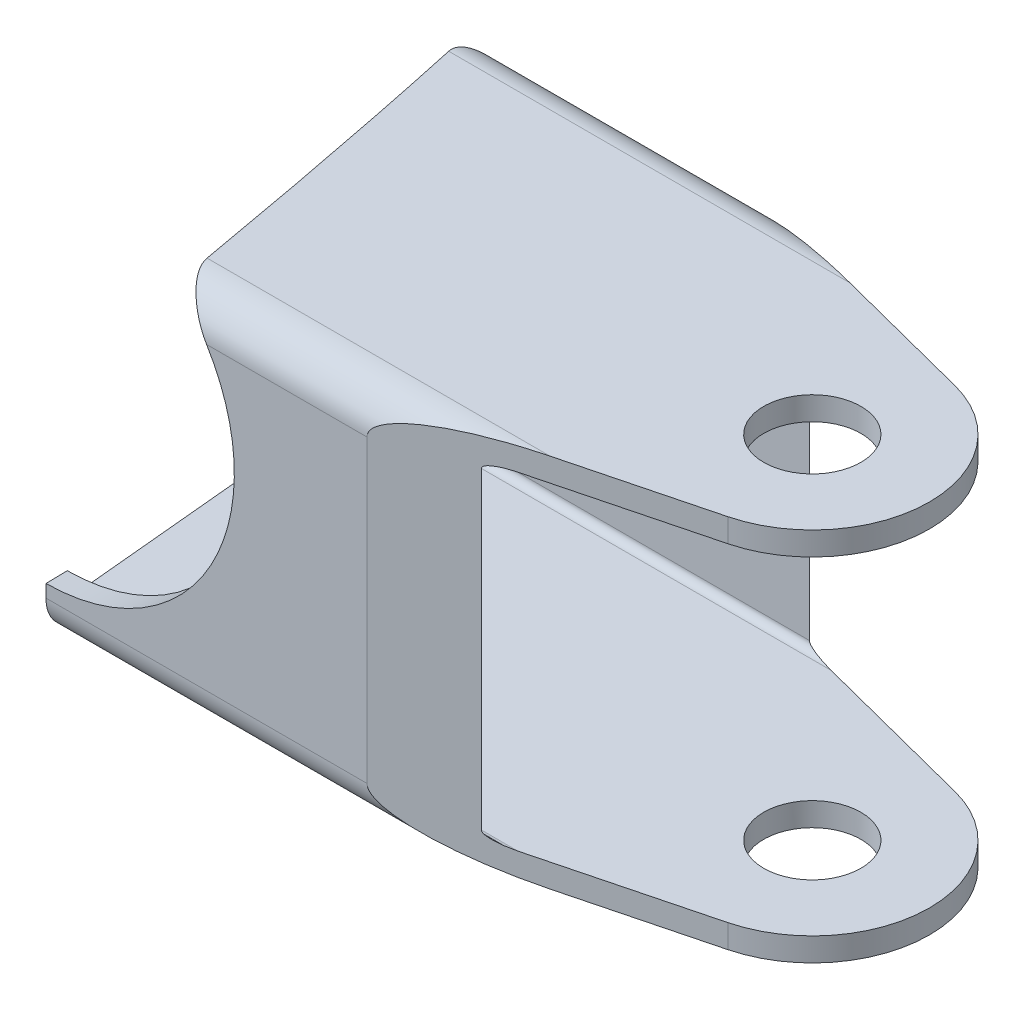
SolidWorks part; units mm, degrees
material "AISI 4130 Steel, annealed at 865C"
ref_plane "Front Plane" through (0, 0, 0) normal (0, 0, 1) x (1, 0, 0)
ref_plane "Top Plane" through (0, 0, 0) normal (0, 1, 0) x (1, 0, 0)
ref_plane "Right Plane" through (0, 0, 0) normal (1, 0, 0) x (0, 0, -1)
sketch "Sketch1" plane through (0, 0, 0) normal (1, 0, 0) x (0, 0, -1)
  line L1 (-10.16, 12.7) -> (10.16, 12.7)
  line L2 (-12.7, 10.16) -> (-12.7, -10.16)
  line L3 (-10.16, -12.7) -> (10.16, -12.7)
  line L4 (12.7, 10.16) -> (12.7, -10.16)
  arc A0 (-10.16, 12.7) -> (-12.7, 10.16) centre (-10.16, 10.16) ccw
  arc A1 (-10.16, -12.7) -> (-12.7, -10.16) centre (-10.16, -10.16) cw
  arc A2 (10.16, 12.7) -> (12.7, 10.16) centre (10.16, 10.16) cw
  arc A3 (12.7, -10.16) -> (10.16, -12.7) centre (10.16, -10.16) cw
  point P4 (0, -12.7)
  point P7 (0, 0)
  point P15 (12.7, 0)
  dimension "D3" = 2.54
  dimension "D4" = 2.54
  dimension "D5" = 2.54
  dimension "D6" = 2.54
  dimension "D1" = 25.4
  dimension "D2" = 20.32
extrude "Boss-Extrude1" add sketch "Sketch1" along normal blind 25.4 and the other way blind 34.925
sketch "Sketch11" plane through (25.4, 0, 0) normal (1, 0, 0) x (0, 0, -1)
  line L0 (-10.16, -12.7) -> (10.16, -12.7) construction
  line L1 (-10.6045, 11.1125) -> (10.6045, 11.1125)
  line L2 (-11.1125, 10.6045) -> (-11.1125, -10.6045)
  line L3 (-10.6045, -11.1125) -> (10.6045, -11.1125)
  line L4 (11.1125, 10.6045) -> (11.1125, -10.6045)
  line L5 (10.16, 12.7) -> (-10.16, 12.7) construction
  line L6 (12.7, -10.16) -> (12.7, 10.16) construction
  line L7 (-12.7, 10.16) -> (-12.7, -10.16) construction
  arc A0 (10.6045, 11.1125) -> (11.1125, 10.6045) centre (10.6045, 10.6045) cw
  arc A1 (10.6045, -11.1125) -> (11.1125, -10.6045) centre (10.6045, -10.6045) ccw
  arc A2 (-11.1125, -10.6045) -> (-10.6045, -11.1125) centre (-10.6045, -10.6045) ccw
  arc A3 (-10.6045, 11.1125) -> (-11.1125, 10.6045) centre (-10.6045, 10.6045) ccw
  dimension "D1" = 1.5875
  dimension "D2" = 1.5875
  dimension "D3" = 1.5875
  dimension "D4" = 1.5875
  dimension "D5" = 0.508
extrude "Cut-Extrude4" cut sketch "Sketch11" against normal through all
sketch "Sketch12" plane through (0, 12.7, 0) normal (0, 1, 0) x (1, 0, 0)
  line L1 (0, 12.7) -> (50.8, 12.7)
  line L2 (50.8, 12.7) -> (50.8, -12.7)
  line L12 (50.8, -12.7) -> (0, -12.7)
  line L13 (19.4444, -7.6861) -> (0, -12.7)
  line L14 (19.4444, 7.6861) -> (0, 12.7)
  line L15 (-34.925, -12.7) -> (25.4, -12.7) construction
  line L16 (-34.925, 12.7) -> (25.4, 12.7) construction
  line L18 (25.4, 10.16) -> (25.4, -10.16) construction
  arc A1 (19.4444, -7.6861) -> (19.4444, 7.6861) centre (17.4625, 0) ccw
  point P8 (18.1688, 9.2165)
  line M6 (-34.925, -10.16) -> (25.4, -10.16)
  line M7 (25.4, -10.16) -> (25.4, 10.16)
  line M8 (25.4, 10.16) -> (-34.925, 10.16)
  line M9 (-34.925, 10.16) -> (-34.925, -10.16)
  dimension "D2" = 50.8
  dimension "D1" = 17.4625
extrude "Cut-Extrude5" cut sketch "Sketch12" against normal through all contours M9 M8 M7 M6 | M7 M8 M9 | M6 M7 region at (34.888, 12.7, 0) region at (20.955, 12.7, -8.1283) region at (20.955, 12.7, 8.1283)
sketch "Sketch14" plane through (0, 12.7, 0) normal (0, 1, 0) x (1, 0, 0)
  circle A0 centre (17.4625, 0) radius 3.2893
  arc A2 (19.4444, -7.6861) -> (19.4444, 7.6861) centre (17.4625, 0) ccw construction
  point P0 (17.4625, 0)
  point P6 (25.4, 0)
  dimension "D2" = 6.5786
  dimension "D1" = 7.9375
  dimension "D3" = 17.4625
extrude "Cut-Extrude6" cut sketch "Sketch14" against normal through all
ref_axis "Axis1" through (-19.7119, 5.0326, 34.3014) along (-0.0934, -0.0736, -0.9929)
ref_point "Point2"
ref_plane "Plane1" through (-21.7437, 3.4321, 12.7) normal (-0.0934, -0.0736, -0.9929) x (-0.9956, 0.0069, 0.0931)
sketch "Sketch15" plane through (-21.7437, 3.4321, 12.7) normal (-0.0934, -0.0736, -0.9929) x (-0.9956, 0.0069, 0.0931)
  circle A0 centre (0, 0) radius 12.7
extrude "Cut-Extrude7" cut sketch "Sketch15" against normal through all both and the other way through all
ref_plane "Plane2" through (-22.7371, 0, 2.1386) normal (-0.9956, 0, 0.0936) x (-0.0934, -0.0736, -0.9929)
sketch "Sketch16" plane through (-22.7371, 0, 2.1386) normal (-0.9956, 0, 0.0936) x (-0.0934, -0.0736, -0.9929)
  line L1 (-26.1696, 25.3576) -> (30.8144, 25.3576)
  line L2 (-26.1696, 25.3576) -> (-26.1696, -24.1606)
  line L3 (-26.1696, -24.1606) -> (30.8144, -24.1606)
  line L4 (30.8144, 25.3576) -> (30.8144, -24.1606)
extrude "Cut-Extrude8" cut sketch "Sketch16" along normal through all
